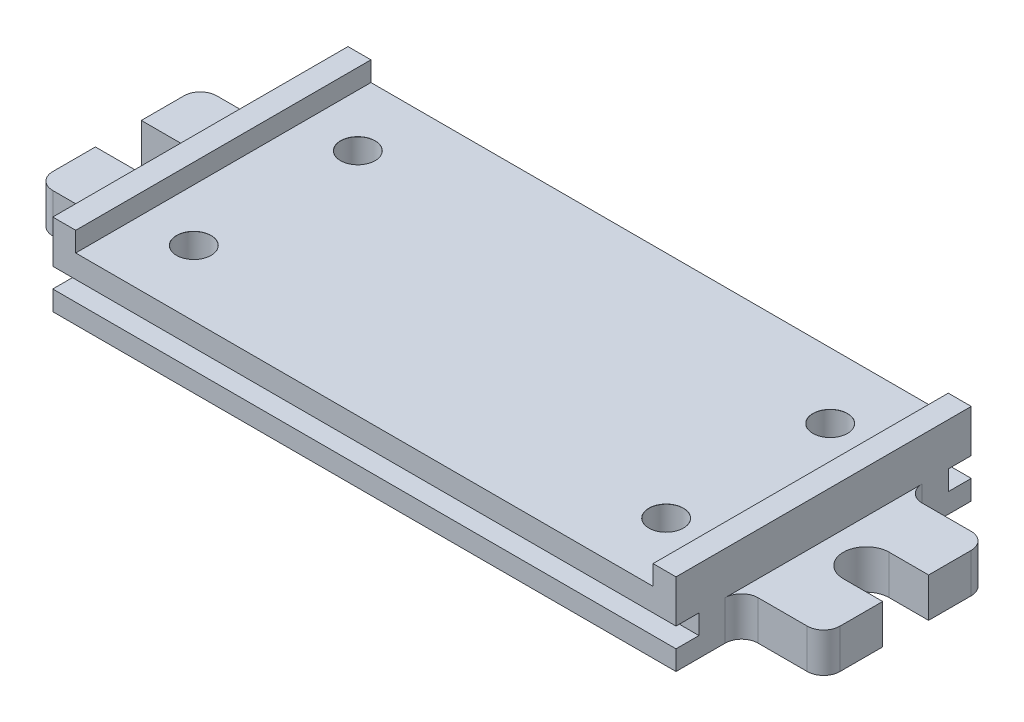
SolidWorks part; units mm, degrees
ref_plane "Front Plane" through (0, 0, 0) normal (0, 0, 1) x (1, 0, 0)
ref_plane "Top Plane" through (0, 0, 0) normal (0, 1, 0) x (1, 0, 0)
ref_plane "Right Plane" through (0, 0, 0) normal (1, 0, 0) x (0, 0, -1)
sketch "Sketch1" plane through (0, 0, 0) normal (0, 1, 0) x (1, 0, 0)
  line L0 (0, 0) -> (0, 47255.8453) construction
  line L1 (0, 0) -> (47255.8453, 0) construction
  line L2 (-100, 25) -> (-115, 25)
  line L3 (95, 45) -> (-95, 45)
  line L4 (95, 45) -> (95, -45)
  line L5 (95, -45) -> (-95, -45)
  line L6 (-95, 45) -> (-95, -45)
  line L7 (95, 45) -> (-95, -45) construction
  line L8 (95, -45) -> (-95, 45) construction
  line L9 (-120, 20) -> (-120, 7)
  line L10 (-120, 7) -> (-108, 7)
  line L11 (-108, -7) -> (-120, -7)
  line L12 (-120, -7) -> (-120, -20)
  line L13 (-115, -25) -> (-100, -25)
  line L14 (115, -25) -> (100, -25)
  line L15 (120, -7) -> (120, -20)
  line L16 (108, -7) -> (120, -7)
  line L17 (120, 7) -> (108, 7)
  line L18 (120, 20) -> (120, 7)
  line L19 (100, 25) -> (115, 25)
  arc A0 (-108, 7) -> (-108, -7) centre (-108, 0) cw
  arc A1 (-115, -25) -> (-120, -20) centre (-115, -20) cw
  arc A2 (-120, 20) -> (-115, 25) centre (-115, 20) cw
  arc A3 (-100, 25) -> (-95, 30) centre (-100, 30) ccw
  arc A4 (-100, -25) -> (-95, -30) centre (-100, -30) cw
  arc A5 (100, -25) -> (95, -30) centre (100, -30) ccw
  arc A6 (100, 25) -> (95, 30) centre (100, 30) cw
  arc A7 (120, 20) -> (115, 25) centre (115, 20) ccw
  arc A8 (115, -25) -> (120, -20) centre (115, -20) ccw
  arc A9 (108, 7) -> (108, -7) centre (108, 0) ccw
  point P5 (0, 0)
  point P25 (-97.9385, -25)
  point P32 (-120, 13.5)
  point P33 (-101, 0)
  dimension "D3" = 5
  dimension "D8" = 5
  dimension "D1" = 190
  dimension "D2" = 90
  dimension "D4" = 20
  dimension "D5" = 25
  dimension "D6" = 14
  dimension "D7" = 19
extrude "Boss-Extrude1" add sketch "Sketch1" along normal blind 25 contours L3 L6 L5 L4 region at (0, 0, 0)
extrude "Boss-Extrude2" add sketch "Sketch1<3>" along normal blind 12 contours L13 A4 L6 A3 L2 A2 L9 L10 A0 L11 L12 A1 | A9 L17 L18 A7 L19 A6 L4 A5 L14 A8 L15 L16 region at (-96.0048, 0, -26.0048) region at (96.0048, 0, -26.0048)
sketch "Sketch1<3>" plane through (0, 0, 0) normal (0, 1, 0) x (1, 0, 0) same geometry as "Sketch1"
sketch "Sketch2" plane through (-95, 0, 0) normal (-1, 0, 0) x (0, 0, 1)
  line L0 (-45, 12) -> (-38, 12)
  line L1 (-45, 25) -> (-45, 0) construction
  line L2 (-38, 12) -> (-38, 6)
  line L3 (-38, 6) -> (-45, 6)
  line L4 (-45, 25) -> (-45, 0)
  line L5 (0, 0) -> (0, 50000) construction
  line L6 (-7, 0) -> (7, 0) construction
  line L7 (45, 25) -> (45, 0)
  line L8 (38, 6) -> (45, 6)
  line L9 (38, 12) -> (38, 6)
  line L10 (45, 12) -> (38, 12)
  point P12 (0, 0)
  line M10 (-45, 25) -> (-45, 0)
  dimension "D1" = 6
  dimension "D2" = 6
  dimension "D3" = 7
extrude "Cut-Extrude1" cut sketch "Sketch2" against normal through all contours L3 L2 L0 M10 | L7 L10 L9 L8 region at (-95, 9, -41.5) region at (-95, 9, 41.5)
sketch "Sketch3" plane through (0, 0, -45) normal (0, 0, -1) x (-1, 0, 0)
  line L0 (0, 0) -> (0, -50000) construction
  line L1 (-95, 0) -> (95, 0) construction
  line L2 (-88, 25) -> (-88, 19)
  line L3 (-95, 25) -> (95, 25) construction
  line L4 (-88, 19) -> (88, 19)
  line L5 (88, 19) -> (88, 25)
  line L6 (-95, 25) -> (95, 25)
  point P4 (0, 0)
  point P11 (-83.6748, 25)
  point P12 (83.2336, 25)
  point P13 (78.5118, 25)
  point P14 (0, 0)
  point P15 (0, 0)
  line M6 (95, 25) -> (-95, 25)
  dimension "D1" = 7
  dimension "D2" = 6
extrude "Cut-Extrude2" cut sketch "Sketch3" against normal through all contours L0 L6 L2 L4 | L0 L4 L5 M6 region at (0, 22, -45)
sketch "Sketch4" plane through (0, 0, 0) normal (0, -1, 0) x (1, 0, 0)
  line L0 (0, 0) -> (0, 50000) construction
  line L1 (0, 0) -> (50000, 0) construction
  line L3 (-77, -30) -> (77, -30)
  line L4 (-82, -25) -> (-82, 25)
  line L5 (-77, 30) -> (77, 30)
  line L6 (82, -25) -> (82, 25)
  line L7 (-82, -30) -> (82, 30) construction
  line L8 (-82, 30) -> (82, -30) construction
  arc A0 (82, 25) -> (77, 30) centre (77, 25) ccw
  arc A1 (77, -30) -> (82, -25) centre (77, -25) ccw
  arc A2 (-77, -30) -> (-82, -25) centre (-77, -25) cw
  arc A3 (-82, 25) -> (-77, 30) centre (-77, 25) cw
  point P5 (0, 0)
  dimension "D3" = 5
  dimension "D1" = 164
  dimension "D2" = 60
extrude "Cut-Extrude3" cut sketch "Sketch4" against normal blind 6
hole_wizard "Hole for M8 300® SC Nuts (SP)1" positions "Sketch5" profile "Sketch6" hole size "M8x1.25" standard "PEM® Metric" end condition through all
sketch "Sketch5" plane through (0, 19, 0) normal (0, 1, 0) x (1, 0, 0)
  line L0 (-88, -45) -> (-88, 45) construction
  line L1 (-88, -45) -> (-88, 45) construction
  line L2 (88, -45) -> (88, 45) construction
  line L3 (88, 45) -> (-88, 45) construction
  line L4 (0, 0) -> (50000, 0) construction
  line L6 (88, -45) -> (-88, -45) construction
  point P0 (-72, 25)
  point P2 (-72, -25)
  point P4 (72, -25)
  point P6 (72, 25)
  point P25 (0, 0)
  point P28 (0, 0)
  dimension "D1" = 16
  dimension "D2" = 16
  dimension "D3" = 16
  dimension "D4" = 16
  dimension "D5" = 20
  dimension "D6" = 20
sketch "Sketch6" plane through (-72, 19, -25) normal (1, 0, 0) x (0, 0, 1)
  line L0 (0, 0) -> (0, 19)
  line L1 (0, 19) -> (5.25, 19)
  line L2 (5.25, 19) -> (5.25, 0.025)
  line L3 (5.25, 0.025) -> (5.275, 0)
  line L5 (5.275, 0) -> (0, 0)
  line L6 (-5.25, 0.025) -> (-5.275, 0) construction
  line L11 (0, -6.35) -> (0, 107.95) construction
  dimension "Thru Hole Dia." = 10.5
  dimension "Thru Hole Depth" = 19
  dimension "Near C'Sink Dia." = 10.55
  dimension "Near C'Sink Angle" = 90
sketch "Sketch7" plane through (0, 6, 0) normal (0, -1, 0) x (1, 0, 0)
  line L0 (-55.1027, 0.3338) -> (62.3303, 0.3338) construction
  line L1 (-24.4338, -13.8211) -> (29.5644, -13.8211) construction
  text T0 "<b>AKASHDIP MAHAPATRA</b>" font "Century Gothic" height in points 28
  text T1 "12/ 5 / 2025" font "Century Gothic" height in points 26
  point P3 (29.5644, -13.8211)
  point P4 (-24.4338, -13.8211)
extrude "Boss-Extrude3" add sketch "Sketch7" along normal blind 5
